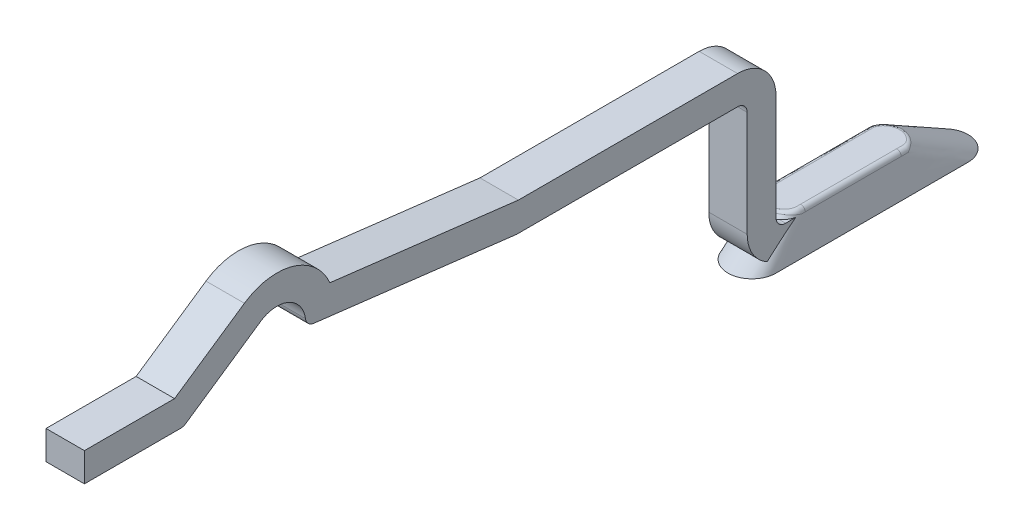
SolidWorks part; units mm, degrees
material "Pure Gold"
ref_plane "Front Plane" through (0, 0, 0) normal (0, 0, 1) x (1, 0, 0)
ref_plane "Top Plane" through (0, 0, 0) normal (0, 1, 0) x (1, 0, 0)
ref_plane "Right Plane" through (0, 0, 0) normal (1, 0, 0) x (0, 0, -1)
ref_plane "Plane1" through (0, -0.05, 0) normal (0, 1, 0) x (1, 0, 0)
sketch "Sketch1" plane through (0, 0, 0) normal (1, 0, 0) x (0, 0, -1)
  line L0 (1.5, 0) -> (0.4, 0)
  line L1 (0.2811, 0) -> (-0.2811, 0) construction
  line L2 (0, 0.4) -> (0, 1.5)
  line L3 (0, 0.2811) -> (0, -0.2811) construction
  line L4 (-0.1, 1.6) -> (-2.4, 1.6)
  line L5 (-2.4, 1.6) -> (-4.5119, 1.8538)
  line L6 (-5.0654, 2.1479) -> (-5.8437, 1.6174)
  line L7 (-5.9, 1.6) -> (-6.9, 1.6)
  arc A0 (0.4, 0) -> (0, 0.4) centre (0.4, 0.4) cw
  arc A1 (0, 1.5) -> (-0.1, 1.6) centre (-0.1, 1.5) ccw
  arc A2 (-4.5991, 1.9398) -> (-5.0654, 2.1479) centre (-4.8965, 1.9) ccw
  arc A3 (-4.5119, 1.8538) -> (-4.5991, 1.9398) centre (-4.5, 1.9531) cw
  arc A4 (-5.8437, 1.6174) -> (-5.9, 1.6) centre (-5.9, 1.7) cw
  point P11 (0, 0)
  point P14 (0, 1.6)
  dimension "D3" = 0.4
  dimension "D4" = 0.1
  dimension "D6" = 0.1
  dimension "D7" = 0.1
  dimension "D9" = 0.3
  dimension "D1" = 1.6
  dimension "D2" = 1.5
  dimension "D5" = 2.4
  dimension "D8" = 5.9
  dimension "D10" = 1
  dimension "D11" = 4.5
  dimension "D12" = 0
  dimension "D13" = 0.3
extrude "Extrude-Thin1" add sketch "Sketch1" along normal mid plane 0.4 thin thin type one direction wall 0.3
sketch "Sketch2" plane through (0, -0.05, 0) normal (0, 1, 0) x (1, 0, 0)
  line L0 (0, 2.25) -> (0, 0.25) construction
  line L1 (0, -1.7919) -> (0, 1.7919) construction
  line L2 (0.25, 2.25) -> (0.25, 0.25)
  line L3 (-0.25, 2.25) -> (-0.25, 0.25)
  line L4 (-0.2811, 0) -> (0.2811, 0) construction
  arc A0 (0.25, 2.25) -> (-0.25, 2.25) centre (0, 2.25) ccw
  arc A1 (-0.25, 0.25) -> (0.25, 0.25) centre (0, 0.25) ccw
  point P5 (0, 1.25)
  dimension "D1" = 0.5
  dimension "D2" = 1.25
  dimension "D3" = 2
ref_plane "Plane2" through (0, 0.35, 0) normal (0, 1, 0) x (1, 0, 0)
sketch "Sketch3" plane through (0, 0.35, 0) normal (0, 1, 0) x (1, 0, 0)
  line L0 (0, 1.6) -> (0, 0.6) construction
  line L1 (0, 2.25) -> (0, 0.25) construction
  line L2 (0.2, 1.6) -> (0.2, 0.6)
  line L3 (-0.2, 1.6) -> (-0.2, 0.6)
  line L4 (-0.2811, 0) -> (0.2811, 0) construction
  arc A0 (0.2, 1.6) -> (-0.2, 1.6) centre (0, 1.6) ccw
  arc A1 (-0.2, 0.6) -> (0.2, 0.6) centre (0, 0.6) ccw
  point P4 (0, 1.1)
  dimension "D2" = 0.2
  dimension "D1" = 1
  dimension "D3" = 1.1
loft "Loft1" add profiles "Sketch3", "Sketch2" connector at (-0.2, 0.35, -1.6) connector at (-0.25, -0.05, -2.25)
fillet "Fillet2" radius 0.05 4 edges
